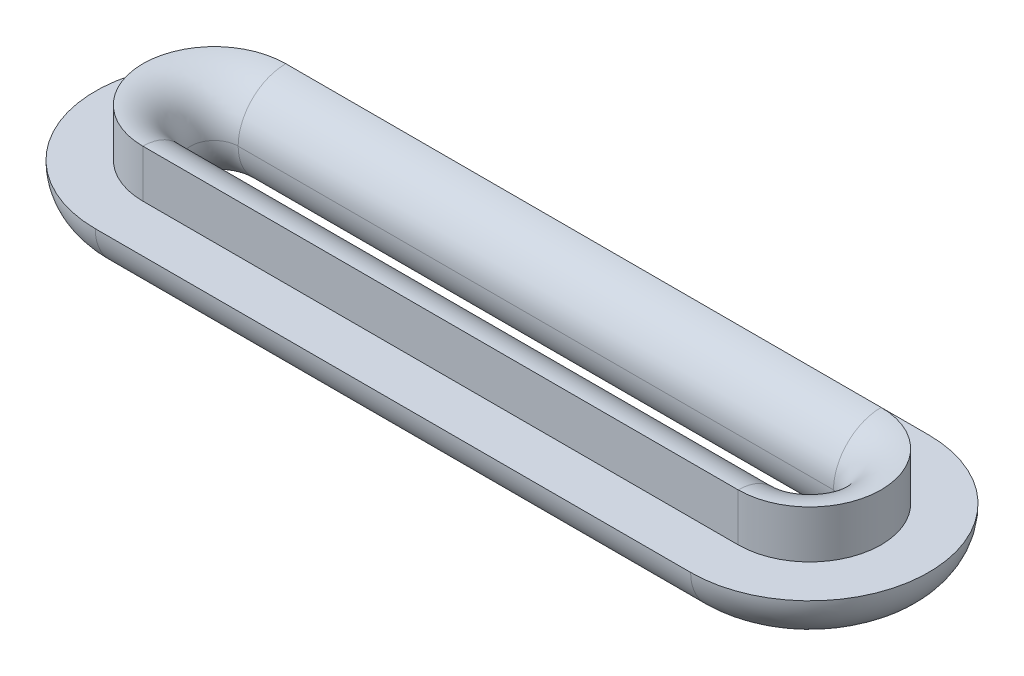
SolidWorks part; units mm, degrees
material "ABS PC"
ref_plane "Front Plane" through (0, 0, 0) normal (0, 0, 1) x (1, 0, 0)
ref_plane "Top Plane" through (0, 0, 0) normal (0, 1, 0) x (1, 0, 0)
ref_plane "Right Plane" through (0, 0, 0) normal (1, 0, 0) x (0, 0, -1)
sketch "Sketch1" plane through (0, 0, 0) normal (0, 1, 0) x (1, 0, 0)
  line L0 (-12.5, 0) -> (12.5, 0) construction
  line L1 (-12.5, 3) -> (12.5, 3)
  line L2 (-12.5, -3) -> (12.5, -3)
  arc A0 (-12.5, 3) -> (-12.5, -3) centre (-12.5, 0) ccw
  arc A1 (12.5, -3) -> (12.5, 3) centre (12.5, 0) ccw
  point P2 (0, 0)
  dimension "D1" = 3
  dimension "D2" = 25
extrude "Extrude-Thin1" add sketch "Sketch1" along normal blind 2 thin thin type one direction reverse wall 2
fillet "Fillet1" radius 2 4 edges at (13.5, 2, 0) (0, 2, 1) (-13.5, 2, 0) (0, 2, -1)
sketch "Sketch2" plane through (0, 0, 0) normal (0, -1, 0) x (1, 0, 0)
  line L0 (12.5, -1) -> (-12.5, -1) construction
  line L1 (-12.5, 1) -> (12.5, 1) construction
  line L2 (12.5, -1) -> (-12.5, -1)
  line L3 (-12.5, 1) -> (12.5, 1)
  line L4 (12.5, -5) -> (-12.5, -5)
  line L5 (-12.5, 5) -> (12.5, 5)
  arc A0 (12.5, -1) -> (12.5, 1) centre (12.5, 0) ccw construction
  arc A1 (-12.5, 1) -> (-12.5, -1) centre (-12.5, 0) ccw construction
  arc A2 (12.5, -1) -> (12.5, 1) centre (12.5, 0) ccw
  arc A3 (-12.5, 1) -> (-12.5, -1) centre (-12.5, 0) ccw
  arc A4 (-12.5, 5) -> (-12.5, -5) centre (-12.5, 0) ccw
  arc A5 (12.5, -5) -> (12.5, 5) centre (12.5, 0) ccw
  dimension "D1" = 4
extrude "Boss-Extrude1" add sketch "Sketch2" along normal blind 2
fillet "Fillet2" radius 2 8 edges at (-13.5, -2, 0) (0, -2, -1) (13.5, -2, 0) (0, -2, 1) (0, -2, -5) (-17.5, -2, 0) (0, -2, 5) (17.5, -2, 0)
